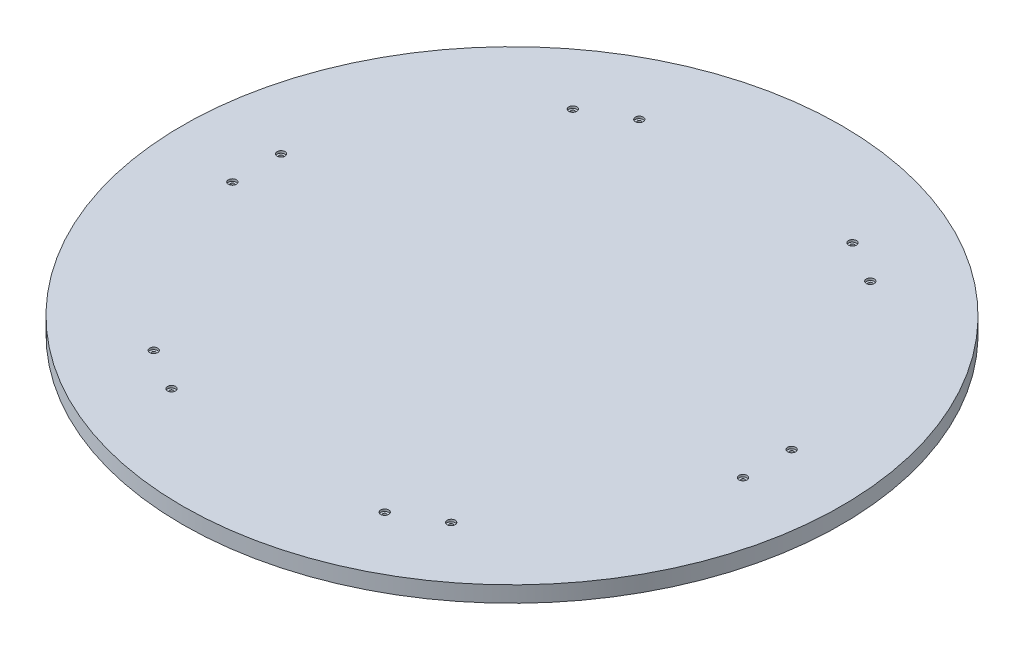
SolidWorks part; units mm, degrees
ref_plane "Front Plane" through (0, 0, 0) normal (0, 0, 1) x (1, 0, 0)
ref_plane "Top Plane" through (0, 0, 0) normal (0, 1, 0) x (1, 0, 0)
ref_plane "Right Plane" through (0, 0, 0) normal (1, 0, 0) x (0, 0, -1)
sketch "Sketch1" plane through (0, 0, 0) normal (0, 1, 0) x (1, 0, 0)
  circle A0 centre (0, 0) radius 261.9375
extrude "Boss-Extrude1" add sketch "Sketch1" along normal blind 12.7
sketch "Sketch6" plane through (0, 0, 0) normal (0, -1, 0) x (1, 0, 0)
  line L0 (203.2, 19.05) -> (203.2, -19.05) construction
  line L1 (215.9, 19.05) -> (215.9, -19.05)
  line L2 (190.5, 19.05) -> (190.5, -19.05)
  line L3 (203.2, -16.5451) -> (201.0307, -17.7976) construction
  line L4 (201.0307, -17.7976) -> (201.0307, -20.3024) construction
  line L5 (201.0307, -20.3024) -> (203.2, -21.5549) construction
  line L6 (203.2, -21.5549) -> (205.3693, -20.3024) construction
  line L7 (205.3693, -20.3024) -> (205.3693, -17.7976) construction
  line L8 (205.3693, -17.7976) -> (203.2, -16.5451) construction
  line L9 (203.2, 22.1294) -> (201.0307, 20.8769) construction
  line L10 (201.0307, 20.8769) -> (201.0307, 18.372) construction
  line L11 (201.0307, 18.372) -> (203.2, 17.1196) construction
  line L12 (203.2, 17.1196) -> (205.3693, 18.372) construction
  line L13 (205.3693, 18.372) -> (205.3693, 20.8769) construction
  line L14 (205.3693, 20.8769) -> (203.2, 22.1294) construction
  line L15 (0, 0) -> (203.2, 0) construction
  line L16 (87.2715, -184.2489) -> (85.1022, -182.9965) construction
  line L17 (85.1022, -182.9965) -> (82.9329, -184.2489) construction
  line L18 (82.9329, -184.2489) -> (82.9329, -186.7538) construction
  line L19 (82.9329, -186.7538) -> (85.1022, -188.0063) construction
  line L20 (85.1022, -188.0063) -> (87.2715, -186.7538) construction
  line L21 (87.2715, -186.7538) -> (87.2715, -184.2489) construction
  line L22 (120.7646, -164.9117) -> (118.5953, -163.6592) construction
  line L23 (118.5953, -163.6592) -> (116.426, -164.9117) construction
  line L24 (116.426, -164.9117) -> (116.426, -167.4166) construction
  line L25 (116.426, -167.4166) -> (118.5953, -168.669) construction
  line L26 (118.5953, -168.669) -> (120.7646, -167.4166) construction
  line L27 (120.7646, -167.4166) -> (120.7646, -164.9117) construction
  line L28 (0, 0) -> (101.6, -175.9764) construction
  line L29 (118.0978, -166.4514) -> (85.1022, -185.5014) construction
  line L30 (124.4478, -177.4499) -> (91.4522, -196.4999)
  line L31 (111.7478, -155.4528) -> (78.7522, -174.5028)
  line L32 (-115.9285, -167.7038) -> (-115.9285, -165.1989) construction
  line L33 (-115.9285, -165.1989) -> (-118.0978, -163.9465) construction
  line L34 (-118.0978, -163.9465) -> (-120.2671, -165.1989) construction
  line L35 (-120.2671, -165.1989) -> (-120.2671, -167.7038) construction
  line L36 (-120.2671, -167.7038) -> (-118.0978, -168.9563) construction
  line L37 (-118.0978, -168.9563) -> (-115.9285, -167.7038) construction
  line L38 (-82.4354, -187.0411) -> (-82.4354, -184.5362) construction
  line L39 (-82.4354, -184.5362) -> (-84.6047, -183.2837) construction
  line L40 (-84.6047, -183.2837) -> (-86.774, -184.5362) construction
  line L41 (-86.774, -184.5362) -> (-86.774, -187.0411) construction
  line L42 (-86.774, -187.0411) -> (-84.6047, -188.2935) construction
  line L43 (-84.6047, -188.2935) -> (-82.4354, -187.0411) construction
  line L44 (0, 0) -> (-101.6, -175.9764) construction
  line L45 (-85.1022, -185.5014) -> (-118.0978, -166.4514) construction
  line L46 (-91.4522, -196.4999) -> (-124.4478, -177.4499)
  line L47 (-78.7522, -174.5028) -> (-111.7478, -155.4528)
  line L48 (-203.2, 16.5451) -> (-201.0307, 17.7976) construction
  line L49 (-201.0307, 17.7976) -> (-201.0307, 20.3024) construction
  line L50 (-201.0307, 20.3024) -> (-203.2, 21.5549) construction
  line L51 (-203.2, 21.5549) -> (-205.3693, 20.3024) construction
  line L52 (-205.3693, 20.3024) -> (-205.3693, 17.7976) construction
  line L53 (-205.3693, 17.7976) -> (-203.2, 16.5451) construction
  line L54 (-203.2, -22.1294) -> (-201.0307, -20.8769) construction
  line L55 (-201.0307, -20.8769) -> (-201.0307, -18.372) construction
  line L56 (-201.0307, -18.372) -> (-203.2, -17.1196) construction
  line L57 (-203.2, -17.1196) -> (-205.3693, -18.372) construction
  line L58 (-205.3693, -18.372) -> (-205.3693, -20.8769) construction
  line L59 (-205.3693, -20.8769) -> (-203.2, -22.1294) construction
  line L60 (0, 0) -> (-203.2, 0) construction
  line L61 (-203.2, -19.05) -> (-203.2, 19.05) construction
  line L62 (-215.9, -19.05) -> (-215.9, 19.05)
  line L63 (-190.5, -19.05) -> (-190.5, 19.05)
  line L64 (-87.2715, 184.2489) -> (-85.1022, 182.9965) construction
  line L65 (-85.1022, 182.9965) -> (-82.9329, 184.2489) construction
  line L66 (-82.9329, 184.2489) -> (-82.9329, 186.7538) construction
  line L67 (-82.9329, 186.7538) -> (-85.1022, 188.0063) construction
  line L68 (-85.1022, 188.0063) -> (-87.2715, 186.7538) construction
  line L69 (-87.2715, 186.7538) -> (-87.2715, 184.2489) construction
  line L70 (-120.7646, 164.9117) -> (-118.5953, 163.6592) construction
  line L71 (-118.5953, 163.6592) -> (-116.426, 164.9117) construction
  line L72 (-116.426, 164.9117) -> (-116.426, 167.4166) construction
  line L73 (-116.426, 167.4166) -> (-118.5953, 168.669) construction
  line L74 (-118.5953, 168.669) -> (-120.7646, 167.4166) construction
  line L75 (-120.7646, 167.4166) -> (-120.7646, 164.9117) construction
  line L76 (0, 0) -> (-101.6, 175.9764) construction
  line L77 (-118.0978, 166.4514) -> (-85.1022, 185.5014) construction
  line L78 (-124.4478, 177.4499) -> (-91.4522, 196.4999)
  line L79 (-111.7478, 155.4528) -> (-78.7522, 174.5028)
  line L80 (115.9285, 167.7038) -> (115.9285, 165.1989) construction
  line L81 (115.9285, 165.1989) -> (118.0978, 163.9465) construction
  line L82 (118.0978, 163.9465) -> (120.2671, 165.1989) construction
  line L83 (120.2671, 165.1989) -> (120.2671, 167.7038) construction
  line L84 (120.2671, 167.7038) -> (118.0978, 168.9563) construction
  line L85 (118.0978, 168.9563) -> (115.9285, 167.7038) construction
  line L86 (82.4354, 187.0411) -> (82.4354, 184.5362) construction
  line L87 (82.4354, 184.5362) -> (84.6047, 183.2837) construction
  line L88 (84.6047, 183.2837) -> (86.774, 184.5362) construction
  line L89 (86.774, 184.5362) -> (86.774, 187.0411) construction
  line L90 (86.774, 187.0411) -> (84.6047, 188.2935) construction
  line L91 (84.6047, 188.2935) -> (82.4354, 187.0411) construction
  line L92 (0, 0) -> (101.6, 175.9764) construction
  line L93 (85.1022, 185.5014) -> (118.0978, 166.4514) construction
  line L94 (91.4522, 196.4999) -> (124.4478, 177.4499)
  line L95 (78.7522, 174.5028) -> (111.7478, 155.4528)
  arc A0 (215.9, 19.05) -> (190.5, 19.05) centre (203.2, 19.05) ccw
  arc A1 (190.5, -19.05) -> (215.9, -19.05) centre (203.2, -19.05) ccw
  circle A2 centre (203.2, -19.05) radius 2.1693 construction
  circle A3 centre (203.2, 19.6245) radius 2.1693 construction
  circle A4 centre (203.2, -19.05) radius 1.524 construction
  circle A5 centre (203.2, 19.6245) radius 1.524 construction
  circle A6 centre (85.1022, -185.5014) radius 2.1693 construction
  circle A7 centre (118.5953, -166.1641) radius 2.1693 construction
  circle A8 centre (85.1022, -185.5014) radius 1.524 construction
  circle A9 centre (118.5953, -166.1641) radius 1.524 construction
  arc A10 (124.4478, -177.4499) -> (111.7478, -155.4528) centre (118.0978, -166.4514) ccw
  arc A11 (78.7522, -174.5028) -> (91.4522, -196.4999) centre (85.1022, -185.5014) ccw
  circle A12 centre (-118.0978, -166.4514) radius 2.1693 construction
  circle A13 centre (-84.6047, -185.7886) radius 2.1693 construction
  circle A14 centre (-118.0978, -166.4514) radius 1.524 construction
  circle A15 centre (-84.6047, -185.7886) radius 1.524 construction
  arc A16 (-91.4522, -196.4999) -> (-78.7522, -174.5028) centre (-85.1022, -185.5014) ccw
  arc A17 (-111.7478, -155.4528) -> (-124.4478, -177.4499) centre (-118.0978, -166.4514) ccw
  circle A18 centre (-203.2, 19.05) radius 2.1693 construction
  circle A19 centre (-203.2, -19.6245) radius 2.1693 construction
  circle A20 centre (-203.2, 19.05) radius 1.524 construction
  circle A21 centre (-203.2, -19.6245) radius 1.524 construction
  arc A22 (-215.9, -19.05) -> (-190.5, -19.05) centre (-203.2, -19.05) ccw
  arc A23 (-190.5, 19.05) -> (-215.9, 19.05) centre (-203.2, 19.05) ccw
  circle A24 centre (-85.1022, 185.5014) radius 2.1693 construction
  circle A25 centre (-118.5953, 166.1641) radius 2.1693 construction
  circle A26 centre (-85.1022, 185.5014) radius 1.524 construction
  circle A27 centre (-118.5953, 166.1641) radius 1.524 construction
  arc A28 (-124.4478, 177.4499) -> (-111.7478, 155.4528) centre (-118.0978, 166.4514) ccw
  arc A29 (-78.7522, 174.5028) -> (-91.4522, 196.4999) centre (-85.1022, 185.5014) ccw
  circle A30 centre (118.0978, 166.4514) radius 2.1693 construction
  circle A31 centre (84.6047, 185.7886) radius 2.1693 construction
  circle A32 centre (118.0978, 166.4514) radius 1.524 construction
  circle A33 centre (84.6047, 185.7886) radius 1.524 construction
  arc A34 (91.4522, 196.4999) -> (78.7522, 174.5028) centre (85.1022, 185.5014) ccw
  arc A35 (111.7478, 155.4528) -> (124.4478, 177.4499) centre (118.0978, 166.4514) ccw
  point P2 (203.2, 0)
  point P32 (101.6, -175.9764)
  point P58 (-101.6, -175.9764)
  point P84 (-203.2, 0)
  point P110 (-101.6, 175.9764)
  point P136 (101.6, 175.9764)
  point P160 (0, 0)
extrude "Cut-Extrude4" cut sketch "Sketch6" against normal blind 6.35
sketch "Sketch7" plane through (0, 6.35, 0) normal (0, -1, 0) x (1, 0, 0)
  line L0 (203.2, 19.05) -> (203.2, -19.05) construction
  line L1 (215.9, 19.05) -> (215.9, -19.05) construction
  line L2 (190.5, 19.05) -> (190.5, -19.05) construction
  line L3 (203.2, -16.5451) -> (201.0307, -17.7976) construction
  line L4 (201.0307, -17.7976) -> (201.0307, -20.3024) construction
  line L5 (201.0307, -20.3024) -> (203.2, -21.5549) construction
  line L6 (203.2, -21.5549) -> (205.3693, -20.3024) construction
  line L7 (205.3693, -20.3024) -> (205.3693, -17.7976) construction
  line L8 (205.3693, -17.7976) -> (203.2, -16.5451) construction
  line L9 (203.2, 22.1294) -> (201.0307, 20.8769) construction
  line L10 (201.0307, 20.8769) -> (201.0307, 18.372) construction
  line L11 (201.0307, 18.372) -> (203.2, 17.1196) construction
  line L12 (203.2, 17.1196) -> (205.3693, 18.372) construction
  line L13 (205.3693, 18.372) -> (205.3693, 20.8769) construction
  line L14 (205.3693, 20.8769) -> (203.2, 22.1294) construction
  line L15 (190.5, -19.05) -> (203.2, -19.05) construction
  line L16 (87.2715, -184.2489) -> (85.1022, -182.9965) construction
  line L17 (85.1022, -182.9965) -> (82.9329, -184.2489) construction
  line L18 (82.9329, -184.2489) -> (82.9329, -186.7538) construction
  line L19 (82.9329, -186.7538) -> (85.1022, -188.0063) construction
  line L20 (85.1022, -188.0063) -> (87.2715, -186.7538) construction
  line L21 (87.2715, -186.7538) -> (87.2715, -184.2489) construction
  line L22 (120.7646, -164.9117) -> (118.5953, -163.6592) construction
  line L23 (118.5953, -163.6592) -> (116.426, -164.9117) construction
  line L24 (116.426, -164.9117) -> (116.426, -167.4166) construction
  line L25 (116.426, -167.4166) -> (118.5953, -168.669) construction
  line L26 (118.5953, -168.669) -> (120.7646, -167.4166) construction
  line L27 (120.7646, -167.4166) -> (120.7646, -164.9117) construction
  line L28 (78.7522, -174.5028) -> (85.1022, -185.5014) construction
  line L29 (118.0978, -166.4514) -> (85.1022, -185.5014) construction
  line L30 (124.4478, -177.4499) -> (91.4522, -196.4999) construction
  line L31 (111.7478, -155.4528) -> (78.7522, -174.5028) construction
  line L32 (-115.9285, -167.7038) -> (-115.9285, -165.1989) construction
  line L33 (-115.9285, -165.1989) -> (-118.0978, -163.9465) construction
  line L34 (-118.0978, -163.9465) -> (-120.2671, -165.1989) construction
  line L35 (-120.2671, -165.1989) -> (-120.2671, -167.7038) construction
  line L36 (-120.2671, -167.7038) -> (-118.0978, -168.9563) construction
  line L37 (-118.0978, -168.9563) -> (-115.9285, -167.7038) construction
  line L38 (-82.4354, -187.0411) -> (-82.4354, -184.5362) construction
  line L39 (-82.4354, -184.5362) -> (-84.6047, -183.2837) construction
  line L40 (-84.6047, -183.2837) -> (-86.774, -184.5362) construction
  line L41 (-86.774, -184.5362) -> (-86.774, -187.0411) construction
  line L42 (-86.774, -187.0411) -> (-84.6047, -188.2935) construction
  line L43 (-84.6047, -188.2935) -> (-82.4354, -187.0411) construction
  line L44 (-111.7478, -155.4528) -> (-118.0978, -166.4514) construction
  line L45 (-85.1022, -185.5014) -> (-118.0978, -166.4514) construction
  line L46 (-91.4522, -196.4999) -> (-124.4478, -177.4499) construction
  line L47 (-78.7522, -174.5028) -> (-111.7478, -155.4528) construction
  line L48 (-203.2, 16.5451) -> (-201.0307, 17.7976) construction
  line L49 (-201.0307, 17.7976) -> (-201.0307, 20.3024) construction
  line L50 (-201.0307, 20.3024) -> (-203.2, 21.5549) construction
  line L51 (-203.2, 21.5549) -> (-205.3693, 20.3024) construction
  line L52 (-205.3693, 20.3024) -> (-205.3693, 17.7976) construction
  line L53 (-205.3693, 17.7976) -> (-203.2, 16.5451) construction
  line L54 (-203.2, -22.1294) -> (-201.0307, -20.8769) construction
  line L55 (-201.0307, -20.8769) -> (-201.0307, -18.372) construction
  line L56 (-201.0307, -18.372) -> (-203.2, -17.1196) construction
  line L57 (-203.2, -17.1196) -> (-205.3693, -18.372) construction
  line L58 (-205.3693, -18.372) -> (-205.3693, -20.8769) construction
  line L59 (-205.3693, -20.8769) -> (-203.2, -22.1294) construction
  line L60 (-190.5, 19.05) -> (-203.2, 19.05) construction
  line L61 (-203.2, -19.05) -> (-203.2, 19.05) construction
  line L62 (-215.9, -19.05) -> (-215.9, 19.05) construction
  line L63 (-190.5, -19.05) -> (-190.5, 19.05) construction
  line L64 (-87.2715, 184.2489) -> (-85.1022, 182.9965) construction
  line L65 (-85.1022, 182.9965) -> (-82.9329, 184.2489) construction
  line L66 (-82.9329, 184.2489) -> (-82.9329, 186.7538) construction
  line L67 (-82.9329, 186.7538) -> (-85.1022, 188.0063) construction
  line L68 (-85.1022, 188.0063) -> (-87.2715, 186.7538) construction
  line L69 (-87.2715, 186.7538) -> (-87.2715, 184.2489) construction
  line L70 (-120.7646, 164.9117) -> (-118.5953, 163.6592) construction
  line L71 (-118.5953, 163.6592) -> (-116.426, 164.9117) construction
  line L72 (-116.426, 164.9117) -> (-116.426, 167.4166) construction
  line L73 (-116.426, 167.4166) -> (-118.5953, 168.669) construction
  line L74 (-118.5953, 168.669) -> (-120.7646, 167.4166) construction
  line L75 (-120.7646, 167.4166) -> (-120.7646, 164.9117) construction
  line L76 (-78.7522, 174.5028) -> (-85.1022, 185.5014) construction
  line L77 (-118.0978, 166.4514) -> (-85.1022, 185.5014) construction
  line L78 (-124.4478, 177.4499) -> (-91.4522, 196.4999) construction
  line L79 (-111.7478, 155.4528) -> (-78.7522, 174.5028) construction
  line L80 (115.9285, 167.7038) -> (115.9285, 165.1989) construction
  line L81 (115.9285, 165.1989) -> (118.0978, 163.9465) construction
  line L82 (118.0978, 163.9465) -> (120.2671, 165.1989) construction
  line L83 (120.2671, 165.1989) -> (120.2671, 167.7038) construction
  line L84 (120.2671, 167.7038) -> (118.0978, 168.9563) construction
  line L85 (118.0978, 168.9563) -> (115.9285, 167.7038) construction
  line L86 (82.4354, 187.0411) -> (82.4354, 184.5362) construction
  line L87 (82.4354, 184.5362) -> (84.6047, 183.2837) construction
  line L88 (84.6047, 183.2837) -> (86.774, 184.5362) construction
  line L89 (86.774, 184.5362) -> (86.774, 187.0411) construction
  line L90 (86.774, 187.0411) -> (84.6047, 188.2935) construction
  line L91 (84.6047, 188.2935) -> (82.4354, 187.0411) construction
  line L92 (111.7478, 155.4528) -> (118.0978, 166.4514) construction
  line L93 (85.1022, 185.5014) -> (118.0978, 166.4514) construction
  line L94 (91.4522, 196.4999) -> (124.4478, 177.4499) construction
  line L95 (78.7522, 174.5028) -> (111.7478, 155.4528) construction
  arc A0 (215.9, 19.05) -> (190.5, 19.05) centre (203.2, 19.05) ccw construction
  arc A1 (190.5, -19.05) -> (215.9, -19.05) centre (203.2, -19.05) ccw construction
  circle A2 centre (203.2, -19.05) radius 2.1693 construction
  circle A3 centre (203.2, 19.6245) radius 2.1693 construction
  circle A4 centre (203.2, -19.05) radius 1.524
  circle A5 centre (203.2, 19.6245) radius 1.524
  circle A6 centre (85.1022, -185.5014) radius 1.524
  circle A7 centre (118.5953, -166.1641) radius 1.524
  circle A8 centre (85.1022, -185.5014) radius 2.1693 construction
  circle A9 centre (118.5953, -166.1641) radius 2.1693 construction
  arc A10 (124.4478, -177.4499) -> (111.7478, -155.4528) centre (118.0978, -166.4514) ccw construction
  arc A11 (78.7522, -174.5028) -> (91.4522, -196.4999) centre (85.1022, -185.5014) ccw construction
  circle A12 centre (-118.0978, -166.4514) radius 1.524
  circle A13 centre (-84.6047, -185.7886) radius 1.524
  circle A14 centre (-118.0978, -166.4514) radius 2.1693 construction
  circle A15 centre (-84.6047, -185.7886) radius 2.1693 construction
  arc A16 (-91.4522, -196.4999) -> (-78.7522, -174.5028) centre (-85.1022, -185.5014) ccw construction
  arc A17 (-111.7478, -155.4528) -> (-124.4478, -177.4499) centre (-118.0978, -166.4514) ccw construction
  circle A18 centre (-203.2, 19.05) radius 1.524
  circle A19 centre (-203.2, -19.6245) radius 1.524
  circle A20 centre (-203.2, 19.05) radius 2.1693 construction
  circle A21 centre (-203.2, -19.6245) radius 2.1693 construction
  arc A22 (-215.9, -19.05) -> (-190.5, -19.05) centre (-203.2, -19.05) ccw construction
  arc A23 (-190.5, 19.05) -> (-215.9, 19.05) centre (-203.2, 19.05) ccw construction
  circle A24 centre (-85.1022, 185.5014) radius 1.524
  circle A25 centre (-118.5953, 166.1641) radius 1.524
  circle A26 centre (-85.1022, 185.5014) radius 2.1693 construction
  circle A27 centre (-118.5953, 166.1641) radius 2.1693 construction
  arc A28 (-124.4478, 177.4499) -> (-111.7478, 155.4528) centre (-118.0978, 166.4514) ccw construction
  arc A29 (-78.7522, 174.5028) -> (-91.4522, 196.4999) centre (-85.1022, 185.5014) ccw construction
  circle A30 centre (118.0978, 166.4514) radius 1.524
  circle A31 centre (84.6047, 185.7886) radius 1.524
  circle A32 centre (118.0978, 166.4514) radius 2.1693 construction
  circle A33 centre (84.6047, 185.7886) radius 2.1693 construction
  arc A34 (91.4522, 196.4999) -> (78.7522, 174.5028) centre (85.1022, 185.5014) ccw construction
  arc A35 (111.7478, 155.4528) -> (124.4478, 177.4499) centre (118.0978, 166.4514) ccw construction
  point P2 (203.2, 0)
  point P33 (101.6, -175.9764)
  point P60 (-101.6, -175.9764)
  point P87 (-203.2, 0)
  point P114 (-101.6, 175.9764)
  point P141 (101.6, 175.9764)
  point P166 (0, 0)
extrude "Cut-Extrude5" cut sketch "Sketch7" against normal through all
sketch "Sketch8" plane through (0, 12.7, 0) normal (0, 1, 0) x (1, 0, 0)
  circle A0 centre (203.2, -19.6245) radius 3.175
  circle A1 centre (203.2, 19.05) radius 3.175
  circle A2 centre (118.0978, -166.4514) radius 3.175
  circle A3 centre (84.6047, -185.7886) radius 3.175
  circle A4 centre (-85.1022, -185.5014) radius 3.175
  circle A5 centre (-118.5953, -166.1641) radius 3.175
  circle A6 centre (-203.2, -19.05) radius 3.175
  circle A7 centre (-203.2, 19.6245) radius 3.175
  circle A8 centre (-118.0978, 166.4514) radius 3.175
  circle A9 centre (-84.6047, 185.7886) radius 3.175
  circle A10 centre (85.1022, 185.5014) radius 3.175
  circle A11 centre (118.5953, 166.1641) radius 3.175
  point P28 (0, 0)
extrude "Cut-Extrude6" cut sketch "Sketch8" against normal blind 1.778
